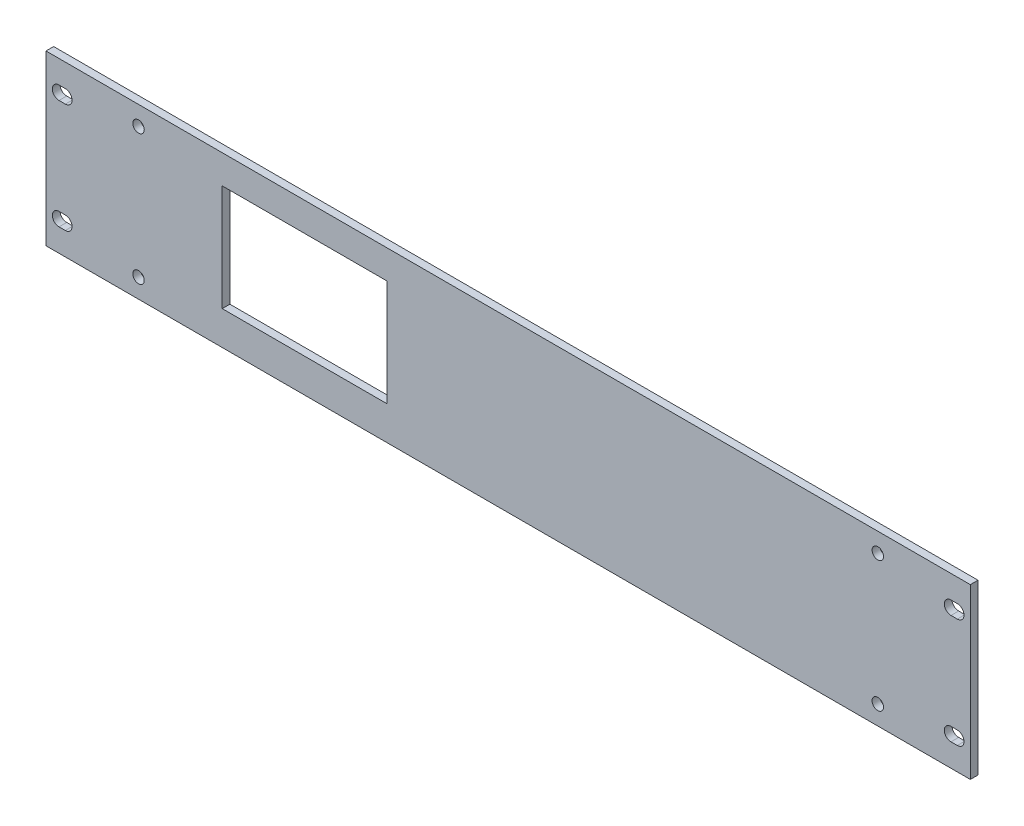
SolidWorks part; units mm, degrees
material "1060 Сплав"
ref_plane "Front" through (0, 0, 0) normal (0, 0, 1) x (1, 0, 0)
ref_plane "Top" through (0, 0, 0) normal (0, 1, 0) x (1, 0, 0)
ref_plane "Right" through (0, 0, 0) normal (1, 0, 0) x (0, 0, -1)
sketch "Эскиз1" plane through (0, 0, 0) normal (0, 0, 1) x (1, 0, 0)
  line L1 (0, 0) -> (482.6, 0)
  line L2 (0, 0) -> (0, 88.1)
  line L3 (0, 88.1) -> (482.6, 88.1)
  line L4 (482.6, 0) -> (482.6, 88.1)
  dimension "D1" = 88.1
  dimension "D2" = 482.6
extrude "Бобышка-Вытянуть1" add sketch "Эскиз1" along normal blind 4
sketch "Эскиз2" plane through (0, 0, 4) normal (0, 0, 1) x (1, 0, 0)
  line L0 (6.8, 72.62) -> (10.1, 72.62) construction
  line L1 (6.8, 76.12) -> (10.1, 76.12)
  line L2 (6.8, 69.12) -> (10.1, 69.12)
  line L3 (0, 88.1) -> (0, 0) construction
  line L4 (482.6, 88.1) -> (0, 88.1) construction
  line L5 (472.5, 72.62) -> (475.8, 72.62) construction
  line L6 (472.5, 76.12) -> (475.8, 76.12)
  line L7 (472.5, 69.12) -> (475.8, 69.12)
  line L8 (472.5, 15.47) -> (475.8, 15.47) construction
  line L9 (472.5, 18.97) -> (475.8, 18.97)
  line L10 (472.5, 11.97) -> (475.8, 11.97)
  line L11 (6.8, 15.47) -> (10.1, 15.47) construction
  line L12 (6.8, 18.97) -> (10.1, 18.97)
  line L13 (6.8, 11.97) -> (10.1, 11.97)
  line L15 (482.6, 0) -> (482.6, 88.1) construction
  arc A0 (6.8, 76.12) -> (6.8, 69.12) centre (6.8, 72.62) ccw
  arc A1 (10.1, 69.12) -> (10.1, 76.12) centre (10.1, 72.62) ccw
  arc A2 (472.5, 76.12) -> (472.5, 69.12) centre (472.5, 72.62) ccw
  arc A3 (475.8, 69.12) -> (475.8, 76.12) centre (475.8, 72.62) ccw
  arc A4 (472.5, 18.97) -> (472.5, 11.97) centre (472.5, 15.47) ccw
  arc A5 (475.8, 11.97) -> (475.8, 18.97) centre (475.8, 15.47) ccw
  arc A6 (6.8, 18.97) -> (6.8, 11.97) centre (6.8, 15.47) ccw
  arc A7 (10.1, 11.97) -> (10.1, 18.97) centre (10.1, 15.47) ccw
  point P2 (8.45, 72.62)
  point P16 (474.15, 72.62)
  point P23 (474.15, 15.47)
  point P30 (8.45, 15.47)
  dimension "D2" = 3.5
  dimension "D4" = 15.48
  dimension "D7" = 6.8
  dimension "D1" = 3.3
  dimension "D3" = 6.8
  dimension "D5" = 2
  dimension "D6" = 2
extrude "Вырез-Вытянуть1" cut sketch "Эскиз2" against normal through all
sketch "Эскиз3" plane through (0, 0, 4) normal (0, 0, 1) x (1, 0, 0)
  line L0 (0, 88.1) -> (0, 0) construction
  line L1 (482.6, 88.1) -> (0, 88.1) construction
  line L2 (0, 0) -> (482.6, 0) construction
  line L3 (482.6, 0) -> (482.6, 88.1) construction
  circle A0 centre (48.3, 78.1) radius 3
  circle A1 centre (434.3, 78.1) radius 3
  circle A2 centre (434.3, 10) radius 3
  circle A3 centre (48.3, 10) radius 3
  dimension "D1" = 6
  dimension "D2" = 48.3
  dimension "D3" = 10
  dimension "D6" = 10
  dimension "D7" = 48.3
  dimension "D4" = 2
  dimension "D5" = 2
extrude "Вырез-Вытянуть2" cut sketch "Эскиз3" against normal through all
sketch "Эскиз4" plane through (0, 0, 4) normal (0, 0, 1) x (1, 0, 0)
  line L0 (0, 88.1) -> (0, 0) construction
  line L1 (92, 73.1) -> (178, 73.1)
  line L2 (92, 73.1) -> (92, 17.6)
  line L3 (92, 17.6) -> (178, 17.6)
  line L4 (178, 73.1) -> (178, 17.6)
  line L5 (482.6, 88.1) -> (0, 88.1) construction
  dimension "D1" = 55.5
  dimension "D2" = 86
  dimension "D3" = 92
  dimension "D4" = 15
extrude "Вырез-Вытянуть3" cut sketch "Эскиз4" against normal through all
